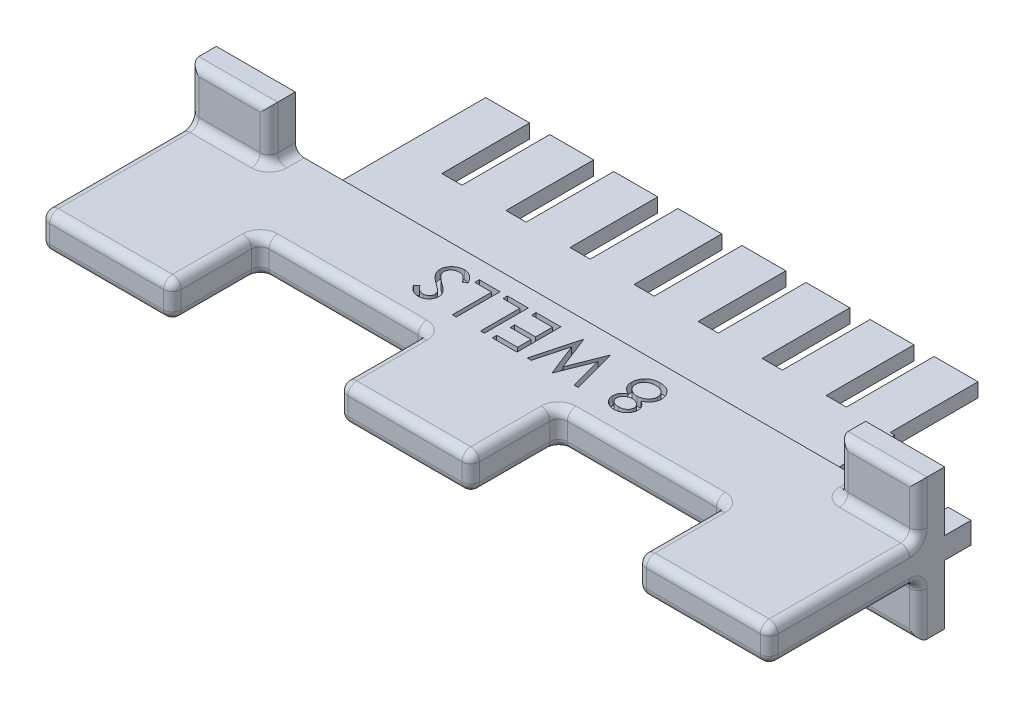
SolidWorks part; units mm, degrees
ref_plane "Front Plane" through (0, 0, 0) normal (0, 0, 1) x (1, 0, 0)
ref_plane "Top Plane" through (0, 0, 0) normal (0, 1, 0) x (1, 0, 0)
ref_plane "Right Plane" through (0, 0, 0) normal (1, 0, 0) x (0, 0, -1)
sketch "Sketch1" plane through (0, 0, 0) normal (0, 0, 1) x (1, 0, 0)
  line L1 (-41.5, 2) -> (41.5, 2)
  line L2 (-41.5, 2) -> (-41.5, -2)
  line L3 (-41.5, -2) -> (41.5, -2)
  line L4 (41.5, 2) -> (41.5, -2)
  line L5 (-41.5, 2) -> (41.5, -2) construction
  line L6 (-41.5, -2) -> (41.5, 2) construction
  point P0 (0, 0)
  dimension "D1" = 83
  dimension "D2" = 4
extrude "Boss-Extrude1" add sketch "Sketch1" along normal blind 10
sketch "Sketch2" plane through (0, 0, 10) normal (0, 0, 1) x (1, 0, 0)
  line L0 (-41.5, -2) -> (41.5, -2) construction
  line L1 (-41.5, 2) -> (-26.5, 2)
  line L2 (-41.5, 2) -> (-41.5, -2)
  line L3 (-41.5, -2) -> (-26.5, -2)
  line L4 (-26.5, 2) -> (-26.5, -2)
  line L6 (41.5, 2) -> (26.5, 2)
  line L7 (41.5, 2) -> (41.5, -2)
  line L8 (41.5, -2) -> (26.5, -2)
  line L9 (26.5, 2) -> (26.5, -2)
  line L10 (-7.5, 2) -> (7.5, 2)
  line L11 (-7.5, 2) -> (-7.5, -2)
  line L12 (-7.5, -2) -> (7.5, -2)
  line L13 (7.5, 2) -> (7.5, -2)
  line L14 (-7.5, 2) -> (7.5, -2) construction
  line L15 (-7.5, -2) -> (7.5, 2) construction
  point P12 (0, 0)
  dimension "D1" = 15
extrude "Boss-Extrude2" add sketch "Sketch2" along normal blind 10
sketch "Sketch3" plane through (0, 0, 0) normal (0, 0, -1) x (-1, 0, 0)
  line L9 (41.5, -1.225) -> (38.9, -1.225)
  line L10 (41.5, -1.225) -> (41.5, 1.225)
  line L11 (41.5, 1.225) -> (38.9, 1.225)
  line L12 (38.9, -1.225) -> (38.9, 1.225)
  line L13 (41.5, -1.225) -> (38.9, 1.225) construction
  line L14 (41.5, 1.225) -> (38.9, -1.225) construction
  line L15 (41.5, 2) -> (41.5, -2) construction
  line L16 (0, 0) -> (0, 13.9589)
  line L17 (-41.5, 1.225) -> (-38.9, -1.225) construction
  line L18 (-41.5, -1.225) -> (-38.9, 1.225) construction
  line L19 (-38.9, -1.225) -> (-38.9, 1.225)
  line L20 (-41.5, 1.225) -> (-38.9, 1.225)
  line L21 (-41.5, -1.225) -> (-41.5, 1.225)
  line L22 (-41.5, -1.225) -> (-38.9, -1.225)
  point P3 (41.5, 0)
  point P10 (40.2, 0)
  point P16 (-40.2, 0)
  line M3 (-41.5, 2) -> (-41.5, -2)
  dimension "D1" = 2.45
  dimension "D2" = 2.6
extrude "Boss-Extrude3" add sketch "Sketch3" along normal blind 3 contours L22 L19 L20 M3 | L12 L11 L10 L9 region at (40.2, 0, 0)
sketch "Sketch4" plane through (0, 0, 0) normal (0, 0, -1) x (-1, 0, 0)
  line L0 (-41.5, -2) -> (-41.5, -1.225) construction
  line L1 (28.3, -0.8) -> (-28.3, -0.8)
  line L2 (28.3, -0.8) -> (28.3, 0.8)
  line L3 (28.3, 0.8) -> (-28.3, 0.8)
  line L4 (-28.3, -0.8) -> (-28.3, 0.8)
  line L5 (28.3, -0.8) -> (-28.3, 0.8) construction
  line L6 (28.3, 0.8) -> (-28.3, -0.8) construction
  point P0 (0, 0)
  dimension "D1" = 1.6
  dimension "D2" = 13.2
extrude "Boss-Extrude4" add sketch "Sketch4" along normal blind 7.5
sketch "Sketch5" plane through (0, 0, -7.5) normal (0, 0, -1) x (-1, 0, 0)
  line L0 (28.3, 0.8) -> (-28.3, 0.8) construction
  line L1 (28.3, -0.8) -> (23.3, -0.8)
  line L2 (28.3, -0.8) -> (28.3, 0.8)
  line L3 (28.3, 0.8) -> (23.3, 0.8)
  line L4 (23.3, -0.8) -> (23.3, 0.8)
  line L33 (21, -0.8) -> (16, -0.8)
  line L34 (21, -0.8) -> (21, 0.8)
  line L35 (21, 0.8) -> (16, 0.8)
  line L36 (16, -0.8) -> (16, 0.8)
  line L37 (13.7, -0.8) -> (8.7, -0.8)
  line L38 (13.7, -0.8) -> (13.7, 0.8)
  line L39 (13.7, 0.8) -> (8.7, 0.8)
  line L40 (8.7, -0.8) -> (8.7, 0.8)
  line L41 (6.4, -0.8) -> (1.4, -0.8)
  line L42 (6.4, -0.8) -> (6.4, 0.8)
  line L43 (6.4, 0.8) -> (1.4, 0.8)
  line L44 (1.4, -0.8) -> (1.4, 0.8)
  line L45 (-0.9, -0.8) -> (-5.9, -0.8)
  line L46 (-0.9, -0.8) -> (-0.9, 0.8)
  line L47 (-0.9, 0.8) -> (-5.9, 0.8)
  line L48 (-5.9, -0.8) -> (-5.9, 0.8)
  line L49 (-8.2, -0.8) -> (-13.2, -0.8)
  line L50 (-8.2, -0.8) -> (-8.2, 0.8)
  line L51 (-8.2, 0.8) -> (-13.2, 0.8)
  line L52 (-13.2, -0.8) -> (-13.2, 0.8)
  line L53 (-15.5, -0.8) -> (-20.5, -0.8)
  line L54 (-15.5, -0.8) -> (-15.5, 0.8)
  line L55 (-15.5, 0.8) -> (-20.5, 0.8)
  line L56 (-20.5, -0.8) -> (-20.5, 0.8)
  line L57 (-22.7999, -0.8) -> (-27.7999, -0.8)
  line L58 (-22.7999, -0.8) -> (-22.7999, 0.8)
  line L59 (-22.7999, 0.8) -> (-27.7999, 0.8)
  line L60 (-27.7999, -0.8) -> (-27.7999, 0.8)
  dimension "D2" = 5
  dimension "D1" = 8
extrude "Boss-Extrude5" add sketch "Sketch5" along normal blind 10
sketch "Sketch6" plane through (0, 0, 0) normal (0, 0, -1) x (-1, 0, 0)
  line L1 (41.5, -2) -> (32.5, -2)
  line L2 (41.5, -2) -> (41.5, -8)
  line L3 (41.5, -8) -> (32.5, -8)
  line L4 (32.5, -2) -> (32.5, -8)
  line L5 (41.5, 2) -> (32.5, 2)
  line L6 (41.5, 2) -> (41.5, 8)
  line L7 (41.5, 8) -> (32.5, 8)
  line L8 (32.5, 2) -> (32.5, 8)
  line L9 (-41.5, -2) -> (-32.5, -2)
  line L10 (-41.5, -2) -> (-41.5, -8)
  line L11 (-41.5, -8) -> (-32.5, -8)
  line L12 (-32.5, -2) -> (-32.5, -8)
  line L13 (-41.5, 2) -> (-32.5, 2)
  line L14 (-41.5, 2) -> (-41.5, 8)
  line L15 (-41.5, 8) -> (-32.5, 8)
  line L16 (-32.5, 2) -> (-32.5, 8)
  dimension "D1" = 6
  dimension "D2" = 9
extrude "Boss-Extrude6" add sketch "Sketch6" against normal blind 3
fillet "Fillet1" radius 1 52 edges at (-41.5, -2, 11.5) (-32.5, -2, 1.5) (-37, -2, 3) (-32.5, -5, 3) (-37, -8, 3) (-41.5, -5, 3) (-26.5, 0, 20) (-34, -2, 20) (-41.5, 0, 20) (-34, 2, 20) (32.5, -2, 1.5) (41.5, -2, 11.5) (41.5, 2, 11.5) (32.5, 2, 1.5) (-32.5, 2, 1.5) (-41.5, 2, 11.5) (37, -8, 3) (32.5, -5, 3) (37, -2, 3) (41.5, -5, 3) (34, -2, 20) (26.5, 0, 20) (34, 2, 20) (41.5, 0, 20) (37, 2, 3) (32.5, 5, 3) (37, 8, 3) (41.5, 5, 3) (0, -2, 20) (-7.5, 0, 20) (0, 2, 20) (7.5, 0, 20) (-37, 8, 3) (-32.5, 5, 3) (-37, 2, 3) (-41.5, 5, 3) (26.5, 2, 15) (26.5, -2, 15) (26.5, 0, 10) (17, -2, 10) (17, 2, 10) (7.5, -2, 15) (7.5, 2, 15) (7.5, 0, 10) (-7.5, 2, 15) (-7.5, -2, 15) (-26.5, -2, 15) (-26.5, 2, 15) (-26.5, 0, 10) (-17, 2, 10) (-7.5, 0, 10) (-17, -2, 10)
ref_plane "Plane1" through (0, 0, 0) normal (0, 1, 0) x (1, 0, 0)
sketch "Sketch7" plane through (0, 2, 0) normal (0, 1, 0) x (1, 0, 0)
  line L0 (30.9142, -2.045) -> (-30.9142, -2.045)
  line L1 (31.5, 0) -> (-31.5, 0) construction
  point P2 (0, -2.045)
  point P5 (0, 0)
sketch "Sketch8" plane through (0, 2, 0) normal (0, 1, 0) x (1, 0, 0)
  text T0 "8 WELLS" font "Century Gothic" height 5
extrude "Cut-Extrude1" cut sketch "Sketch8" against normal blind 1
